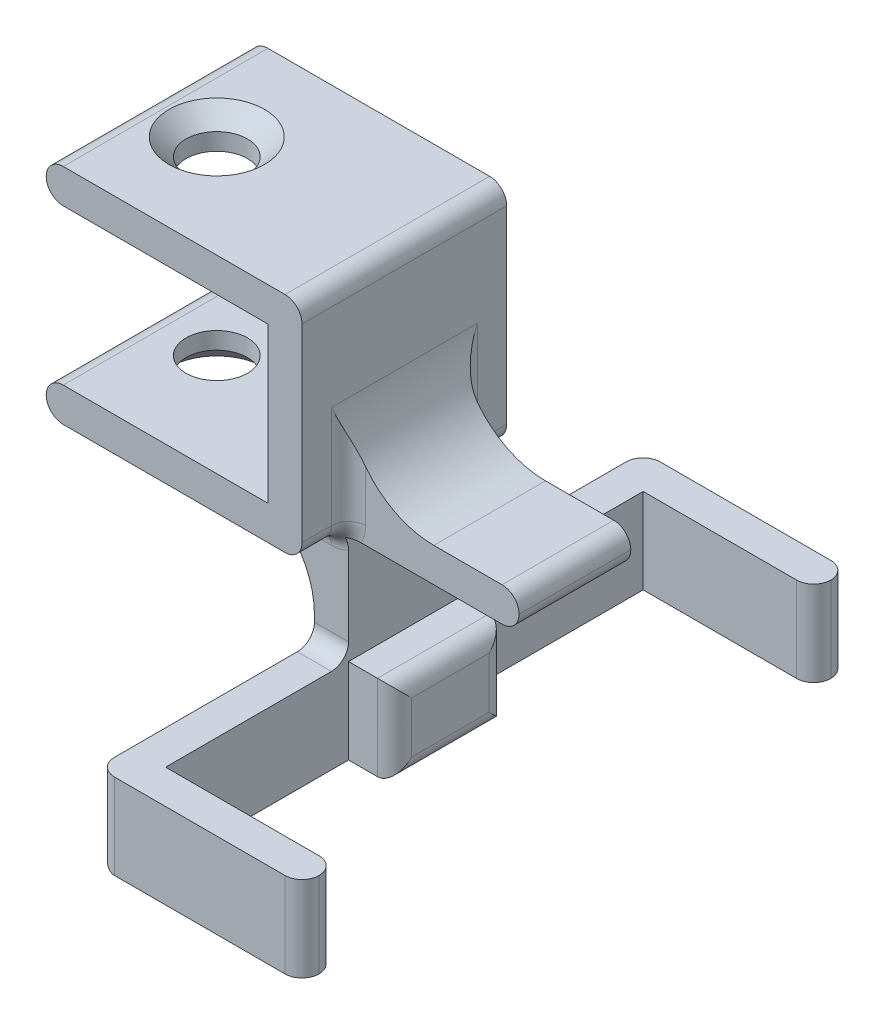
SolidWorks part; units mm, degrees
ref_plane "Front Plane" through (0, 0, 0) normal (0, 0, 1) x (1, 0, 0)
ref_plane "Top Plane" through (0, 0, 0) normal (0, 1, 0) x (1, 0, 0)
ref_plane "Right Plane" through (0, 0, 0) normal (1, 0, 0) x (0, 0, -1)
sketch "Sketch1" plane through (0, 0, 0) normal (0, 0, 1) x (1, 0, 0)
  line L1 (0, 0) -> (-13, 0)
  line L2 (0, 0) -> (0, -9.1)
  line L3 (0, -9.1) -> (-13, -9.1)
  line L4 (-13, 2) -> (-13, 0)
  line L5 (2, -11.1) -> (-13, -11.1)
  line L6 (2, 2) -> (2, -11.1)
  line L7 (2, 2) -> (-13, 2)
  line L8 (0, 0) -> (-13, 0) construction
  line L9 (-13, 0) -> (-13, -9.1) construction
  line L10 (2, 2) -> (-15, 2) construction
  line L11 (-15, 2) -> (-15, -11.1) construction
  line L12 (-13, -9.1) -> (-13, -11.1)
  line L13 (2, -11.1) -> (-15, -11.1) construction
  line L14 (2, -11.1) -> (2, -17.5)
  line L15 (2, -17.5) -> (4.7, -17.5)
  line L16 (0, -11.1) -> (0, -22.5)
  line L17 (0, -22.5) -> (4.7, -22.5)
  line L18 (4.7, -17.5) -> (4.7, -22.5)
  line L19 (2, -11.1) -> (12, -11.1)
  line L20 (12, -11.1) -> (12, -9.1)
  line L21 (12, -9.1) -> (2, -9.1)
  point P18 (0, -22.35)
  dimension "D1" = 9.1
  dimension "D2" = 13
  dimension "D4" = 2
  dimension "D7" = 10
  dimension "D8" = 5
  dimension "D5" = 2.7
  dimension "D6" = 6.4
  dimension "D3" = 2
extrude "Boss-Extrude1" add sketch "Sketch1" along normal mid plane 6.55 contours L3 L12 L5 L6 L7 L4 L1 L2 | L5 L17 | L6 region at (-6.5, 0.1992, 0) region at (7, -10.1, 0) region at (1.874, -17.9901, 0)
extrude "Boss-Extrude2" add sketch "Sketch1<3>" along normal mid plane 12 contours L3 L12 L5 L6 L7 L4 L1 L2 region at (-6.5, 0.1992, 0)
sketch "Sketch1<3>" plane through (0, 0, 0) normal (0, 0, 1) x (1, 0, 0) same geometry as "Sketch1"
sketch "Sketch3" plane through (0, 0, 0) normal (0, 0, 1) x (1, 0, 0)
  line L0 (2, -17.5) -> (2, -22.5)
  line L1 (2, -17.5) -> (0, -17.5)
  line L6 (2, -11.1) -> (0, -11.1)
  line L7 (0, -11.1) -> (0, -22.5)
  line L8 (0, -22.5) -> (4.7, -22.5)
  line L9 (4.7, -22.5) -> (4.7, -17.5)
  line L10 (4.7, -17.5) -> (2, -17.5)
  line L11 (2, -17.5) -> (2, -11.1)
  line L12 (2, -11.1) -> (0, -11.1)
  line L13 (0, -11.1) -> (0, -22.5)
  line L14 (0, -22.5) -> (4.7, -22.5)
  line L15 (4.7, -22.5) -> (4.7, -17.5)
  line L16 (4.7, -17.5) -> (2, -17.5)
  line L17 (2, -17.5) -> (2, -11.1)
  dimension "D1" = 0
extrude "Boss-Extrude3" add sketch "Sketch3" along normal mid plane 32 contours L13 L14 L0 L1 region at (1, -20, 0)
sketch "Sketch4" plane through (2, 0, 0) normal (1, 0, 0) x (0, 0, -1)
  line L0 (-16, -22.5) -> (-3.275, -22.5) construction
  line L1 (-16, -17.5) -> (-14, -17.5)
  line L2 (-16, -17.5) -> (-16, -22.5)
  line L3 (-16, -22.5) -> (-14, -22.5)
  line L4 (-14, -17.5) -> (-14, -22.5)
  line L5 (3.275, -22.5) -> (16, -22.5) construction
  line L6 (16, -17.5) -> (14, -17.5)
  line L7 (16, -17.5) -> (16, -22.5)
  line L8 (16, -22.5) -> (14, -22.5)
  line L9 (14, -17.5) -> (14, -22.5)
  dimension "D1" = 2
  dimension "D2" = 2
extrude "Boss-Extrude4" add sketch "Sketch4" along normal blind 10
fillet "Fillet1" radius 1 22 edges at (-13, -11.1, 0) (-13, -9.1, 0) (-13, 0, 0) (-13, 2, 0) (2, 2, 0) (12, -11.1, 0) (0, -22.5, 0) (4.7, -22.5, 0) (12, -9.1, 0) (2, -11.1, -4.6375) (2, -11.1, 4.6375) (1, -17.5, -3.275) (1, -17.5, 3.275) (4.7, -20, 3.275) (4.7, -20, -3.275) (0, -20, -16) (0, -20, 16) (12, -20, 14) (12, -20, 16) (12, -20, -16) (12, -20, -14) (4.7, -17.5, 0)
fillet "Fillet2" radius 1 4 edges at (2, -9.6, 3.275) (0.5, -11.1, 3.275) (1.7071, -10.8071, -3.275) (1.7071, -10.8071, 3.275)
sketch "Sketch2" plane through (0, 2, 0) normal (0, 1, 0) x (1, 0, 0)
  line L0 (-12, 6) -> (-12, -6) construction
  circle A0 centre (-9, 0) radius 1.8
  point P6 (-12, 0)
  dimension "D2" = 3.6
  dimension "D1" = 9
extrude "Cut-Extrude1" cut sketch "Sketch2" against normal through all both and the other way through all
chamfer "Chamfer1" distance 1 angle 45 2 edges at (-7.2, -11.1, 0) (-7.2, 2, 0)
fillet "Fillet3" radius 5 2 edges at (0, -11.1, 0) (2, -9.1, 0)
